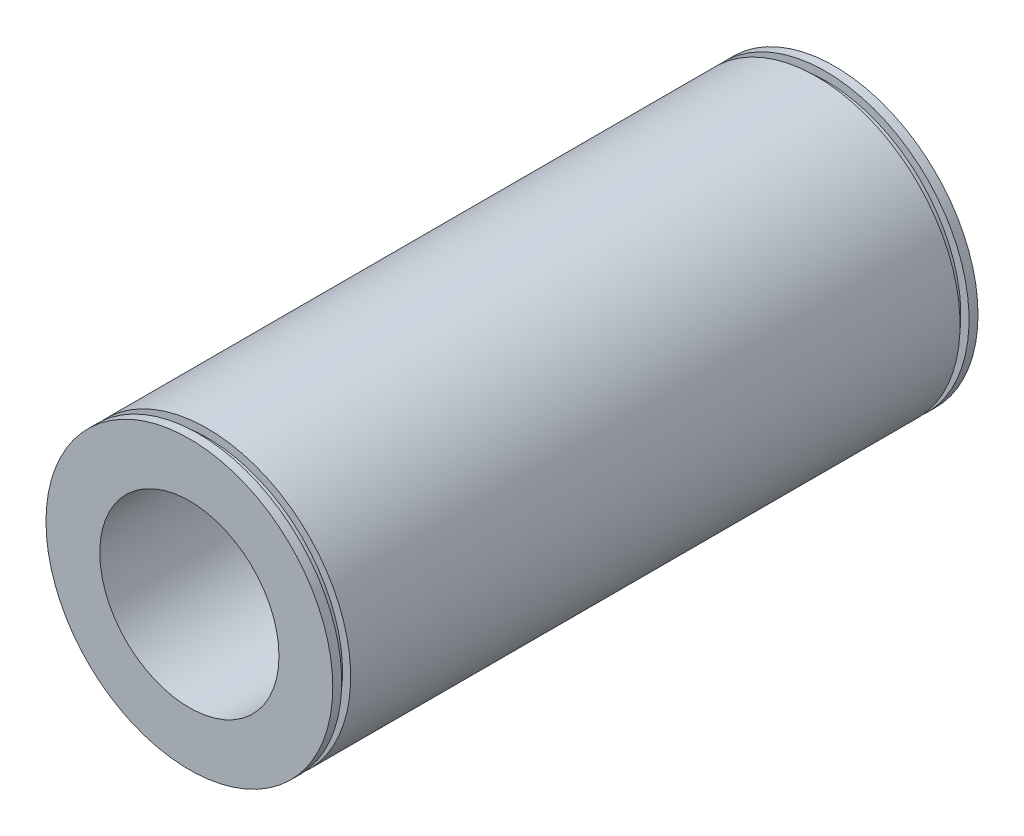
SolidWorks part; units mm, degrees
ref_plane "Front Plane" through (0, 0, 0) normal (0, 0, 1) x (1, 0, 0)
ref_plane "Top Plane" through (0, 0, 0) normal (0, 1, 0) x (1, 0, 0)
ref_plane "Right Plane" through (0, 0, 0) normal (1, 0, 0) x (0, 0, -1)
sketch "Sketch1" plane through (0, 0, 0) normal (0, 0, 1) x (1, 0, 0)
  circle A0 centre (0, 0) radius 25.4
  circle A1 centre (0, 0) radius 15.875
  circle A2 centre (0, 0) radius 23.9522 construction
  point P6 (0, 23.9522)
  point P7 (0, 0)
  dimension "D1" = 50.8
  dimension "D2" = 31.75
  dimension "D3" = 47.9044
extrude "Boss-Extrude1" add sketch "Sketch1" along normal mid plane 114.3
sketch "Sketch2" plane through (0, 0, 0) normal (1, 0, 0) x (0, 0, -1)
  line L0 (-57.15, 25.4) -> (-57.15, -25.4) construction
  line L1 (-55.5625, 25.4) -> (-53.975, 25.4)
  line L2 (-55.5625, 25.4) -> (-55.5625, 23.9522)
  line L3 (-55.5625, 23.9522) -> (-53.975, 23.9522)
  line L4 (-53.975, 25.4) -> (-53.975, 23.9522)
  line L5 (0, 23.9522) -> (0, -23.9522) construction
  line L6 (0, 0) -> (-75.0133, 0) construction
  line L9 (-57.15, 23.9522) -> (0, 23.9522) construction
  point P13 (-55.5625, 22.5765)
  point P14 (-53.975, 15.8737)
  dimension "D1" = 1.5875
  dimension "D2" = 1.5875
  dimension "D4" = 25.4
revolve "Cut-Revolve1" cut sketch "Sketch2" angle 360 about L6
mirror "Mirror1" about plane through (0, 0, 0) normal (0, 0, 1) of "Cut-Revolve1"
